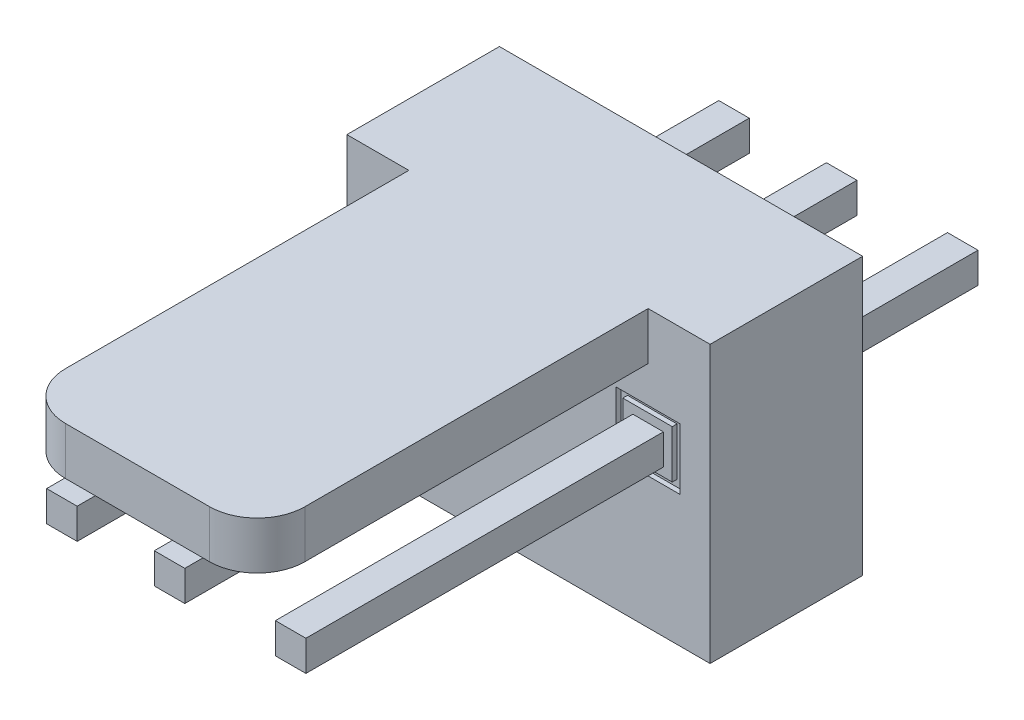
SolidWorks part; units mm, degrees
note: The reader was unsure of these and kept them because the rebuilt part matched: shared geometry of "Эскиз1<3>".
ref_plane "Спереди" through (0, 0, 0) normal (0, 0, 1) x (1, 0, 0)
ref_plane "Сверху" through (0, 0, 0) normal (0, 1, 0) x (1, 0, 0)
ref_plane "Справа" through (0, 0, 0) normal (1, 0, 0) x (0, 0, -1)
sketch "Эскиз1" plane through (0, 0, 0) normal (0, 0, 1) x (1, 0, 0)
  line L0 (0, 0.32) -> (0, -0.32) construction
  line L1 (-0.32, 0.32) -> (0.32, 0.32)
  line L2 (-0.32, 0.32) -> (-0.32, -0.32)
  line L3 (-0.32, -0.32) -> (0.32, -0.32)
  line L4 (0.32, 0.32) -> (0.32, -0.32)
  line L5 (-0.32, 0) -> (0.32, 0) construction
  line L6 (-2.86, 0.32) -> (-2.22, 0.32)
  line L7 (-2.86, 0.32) -> (-2.86, -0.32)
  line L8 (-2.86, -0.32) -> (-2.22, -0.32)
  line L9 (-2.22, 0.32) -> (-2.22, -0.32)
  line L10 (-2.54, 0.32) -> (-2.54, -0.32) construction
  line L11 (-2.86, 0) -> (-2.22, 0) construction
  line L12 (-5.4, 0.32) -> (-5.4, -0.32) [skipped]
  line L13 (-5.4, -0.32) -> (-4.76, -0.32) [skipped]
  line L14 (-4.76, 0.32) -> (-4.76, -0.32) [skipped]
  line L15 (-5.08, 0.32) -> (-5.08, -0.32) construction
  line L16 (-5.4, 0) -> (-4.76, 0) construction
  line L17 (-7.94, 0.32) -> (-7.3, 0.32) [skipped]
  line L18 (-7.94, 0.32) -> (-7.94, -0.32) [skipped]
  line L19 (-7.94, -0.32) -> (-7.3, -0.32) [skipped]
  line L20 (-7.3, 0.32) -> (-7.3, -0.32) [skipped]
  line L21 (-7.62, 0.32) -> (-7.62, -0.32) construction
  line L22 (-7.94, 0) -> (-7.3, 0) construction
  line L23 (-10.48, 0.32) -> (-9.84, 0.32) [skipped]
  line L24 (-10.48, 0.32) -> (-10.48, -0.32) [skipped]
  line L25 (-10.48, -0.32) -> (-9.84, -0.32) [skipped]
  line L26 (-9.84, 0.32) -> (-9.84, -0.32) [skipped]
  line L27 (-10.16, 0.32) -> (-10.16, -0.32) construction
  line L28 (-10.48, 0) -> (-9.84, 0) construction
  line L29 (-2.54, 0) -> (-6.0519, 0) construction
  line L30 (-13.02, 0.32) -> (-13.02, -0.32) [skipped]
  line L31 (-13.02, -0.32) -> (-12.38, -0.32) [skipped]
  line L32 (-12.38, 0.32) -> (-12.38, -0.32) [skipped]
  line L33 (-12.7, 0.32) -> (-12.7, -0.32) construction
  line L34 (-13.02, 0) -> (-12.38, 0) construction
  line L35 (-5.4, 0.32) -> (-4.76, 0.32) [skipped]
  line L36 (-13.02, 0.32) -> (-12.38, 0.32) [skipped]
  line L37 (-5.1182, 0.32) -> (-4.4782, 0.32)
  line L38 (-5.1182, 0.32) -> (-5.1182, -0.32)
  line L39 (-5.1182, -0.32) -> (-4.4782, -0.32)
  line L40 (-4.4782, 0.32) -> (-4.4782, -0.32)
  line L41 (-5.08, 0.32) -> (-5.08, -0.32) construction
  line L42 (-5.1182, 0) -> (-4.4782, 0) construction
  dimension "D1" = 0.64
  dimension "D2" = 0.64
  dimension "D3" = 2.54
  dimension "D4" = 2.54
sketch "Эскиз2" plane through (0, 0, 0) normal (0, 0, 1) x (1, 0, 0)
  line L0 (-6.32, -0.5) -> (1.3, -0.5) construction
  line L7 (-6.32, 2.4) -> (-6.32, -3.4)
  line L8 (1.3, -3.4) -> (-6.32, -3.4)
  line L9 (1.3, 2.4) -> (1.3, -3.4)
  line L10 (1.3, 2.4) -> (-6.32, 2.4)
  dimension "D1" = 7.62
  dimension "D2" = 0.5
  dimension "D3" = 1.3
  dimension "D4" = 5.8
extrude "Вытянуть1" add sketch "Эскиз2" along normal blind 3.2
sketch "Эскиз3" plane through (0, 0, 3.2) normal (0, 0, 1) x (1, 0, 0)
  line L0 (-2.51, 2.4) -> (-2.51, 1.4) construction
  line L1 (-5.02, 2.4) -> (0, 2.4)
  line L2 (0, 2.4) -> (0, 1.4)
  line L3 (-5.02, 1.4) -> (0, 1.4)
  line L4 (-6.32, 2.4) -> (-6.32, -3.4) construction
  line L7 (-5.02, 2.4) -> (-5.02, 1.4)
  dimension "D1" = 1.3
  dimension "D2" = 1
extrude "Вытянуть4" add sketch "Эскиз3" along normal blind 8.2
fillet "Скругление1" radius 1 2 edges at (0, 1.9, 11.4) (-5.02, 1.9, 11.4)
extrude "Вытянуть5" add sketch "Эскиз1" along normal blind 10.7
extrude "Вытянуть6" add sketch "Эскиз1<3>" against normal blind 3.4
sketch "Эскиз1<3>" plane through (0, 0, 0) normal (0, 0, 1) x (1, 0, 0) same geometry as "Эскиз1"
sketch "Эскиз4" plane through (-0.7659, 1.722, 3.2) normal (0, 0, 1) x (1, 0, 0)
  line L1 (0.2338, -1.2149) -> (1.2715, -1.2149)
  line L2 (0.2338, -1.2149) -> (0.2338, -2.2219)
  line L3 (0.2338, -2.2219) -> (1.2715, -2.2219)
  line L4 (1.2715, -1.2149) -> (1.2715, -2.2219)
  line L5 (0.0923, -1.0824) -> (1.4303, -1.0824)
  line L6 (0.0923, -1.0824) -> (0.0923, -2.3644)
  line L7 (0.0923, -2.3644) -> (1.4303, -2.3644)
  line L8 (1.4303, -1.0824) -> (1.4303, -2.3644)
extrude "Вырез-Вытянуть1" cut sketch "Эскиз4" against normal blind 0.1
sketch "Эскиз5" plane through (0, 0, -3.4) normal (0, 0, -1) x (-1, 0, 0)
  line L0 (2.54, 0) -> (3.68, 0) construction
  line L1 (2.54, 0) -> (2.54, 0.9603) construction
  line L2 (2.22, -0.32) -> (2.22, 0.32) construction
  line L3 (2.86, 0.32) -> (2.86, -0.32) construction
  line L4 (2.86, -0.32) -> (2.22, -0.32) construction
  line L5 (2.22, 0.32) -> (2.86, 0.32) construction
  circle A0 centre (2.54, 0) radius 0.1559
extrude "Вырез-Вытянуть2" cut sketch "Эскиз5" against normal blind 2
